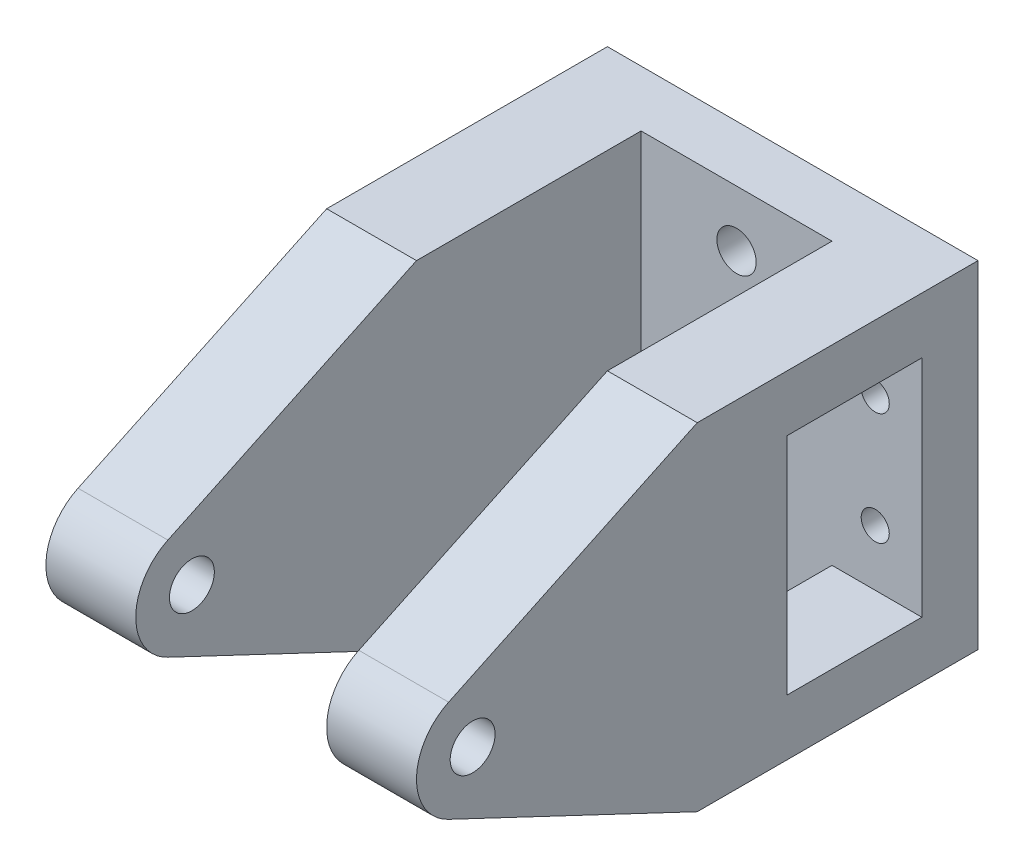
SolidWorks part; units mm, degrees
ref_plane "正面(Front)" through (0, 0, 0) normal (0, 0, 1) x (1, 0, 0)
ref_plane "平面(Top)" through (0, 0, 0) normal (0, 1, 0) x (1, 0, 0)
ref_plane "右側面(Right)" through (0, 0, 0) normal (1, 0, 0) x (0, 0, -1)
sketch "ｽｹｯﾁ1" plane through (0, 0, 0) normal (0, 0, 1) x (1, 0, 0)
  line L1 (-16.5, 15) -> (16.5, 15)
  line L2 (-16.5, 15) -> (-16.5, -15)
  line L3 (-16.5, -15) -> (16.5, -15)
  line L4 (16.5, 15) -> (16.5, -15)
  line L5 (-16.5, 15) -> (16.5, -15) construction
  line L6 (-16.5, -15) -> (16.5, 15) construction
  point P0 (0, 0)
  dimension "D1" = 33
  dimension "D2" = 30
extrude "ﾎﾞｽ - 押し出し1" add sketch "ｽｹｯﾁ1" along normal blind 5
sketch "ｽｹｯﾁ3" plane through (16.5, 0, 0) normal (1, 0, 0) x (0, 0, -1)
  line L0 (-5, 15) -> (-25, 15)
  line L1 (-25, 15) -> (-47.1394, 4.5192)
  line L2 (0, 0) -> (-92.7849, 0) construction
  line L3 (-5, -15) -> (-5, 15) construction
  line L4 (-25, -15) -> (-47.1394, -4.5192)
  line L5 (-5, -15) -> (-25, -15)
  line L6 (-5, -15) -> (-5, 15)
  arc A0 (-47.1394, 4.5192) -> (-47.1394, -4.5192) centre (-45, 0) ccw
  circle A1 centre (-45, 0) radius 2
  dimension "D2" = 5
  dimension "D4" = 4
  dimension "D1" = 40
  dimension "D3" = 20
extrude "ﾎﾞｽ - 押し出し2" add sketch "ｽｹｯﾁ3" against normal blind 8
mirror "ﾐﾗｰ1" about plane through (0, 0, 0) normal (1, 0, 0) of "ﾎﾞｽ - 押し出し2"
sketch "ｽｹｯﾁ4" plane through (0, 0, 5) normal (0, 0, 1) x (1, 0, 0)
  line L0 (0, 0) -> (26.7416, 0) construction
  line L1 (0, 0) -> (0, 23.9443) construction
  line L2 (8.5, 15) -> (-8.5, 15) construction
  circle A0 centre (0, 10) radius 1.75
  circle A1 centre (0, -10) radius 1.75
  dimension "D1" = 3.5
  dimension "D2" = 5
extrude "ｶｯﾄ - 押し出し1" cut sketch "ｽｹｯﾁ4" against normal through all
sketch "ｽｹｯﾁ5" plane through (0, 0, 0) normal (0, 0, 1) x (1, 0, 0)
  circle A0 centre (12.35, -5) radius 1.75 construction
  circle A1 centre (12.35, -5) radius 1.75 construction
  circle A2 centre (12.35, 5) radius 1.75 construction
  circle A3 centre (12.35, 5) radius 1.75 construction
  circle A4 centre (12.35, -5) radius 1.25
  circle A5 centre (12.35, 5) radius 1.25
  dimension "D1" = 2.5
extrude "ｶｯﾄ - 押し出し2" cut sketch "ｽｹｯﾁ5" along normal blind 5
sketch "ｽｹｯﾁ6" plane through (16.5, 0, 0) normal (1, 0, 0) x (0, 0, -1)
  line L0 (0, 0) -> (-33.2812, 0) construction
  line L1 (-25, 15) -> (0, 15) construction
  line L2 (-17, 10) -> (-5, 10)
  line L3 (-17, 10) -> (-17, -10)
  line L4 (-17, -10) -> (-5, -10)
  line L5 (-5, 10) -> (-5, -10)
  line L6 (-17, 10) -> (-5, -10) construction
  line L7 (-17, -10) -> (-5, 10) construction
  point P3 (-11, 0)
  dimension "D1" = 5
  dimension "D2" = 5
  dimension "D3" = 12
extrude "ｶｯﾄ - 押し出し3" cut sketch "ｽｹｯﾁ6" against normal up to next
